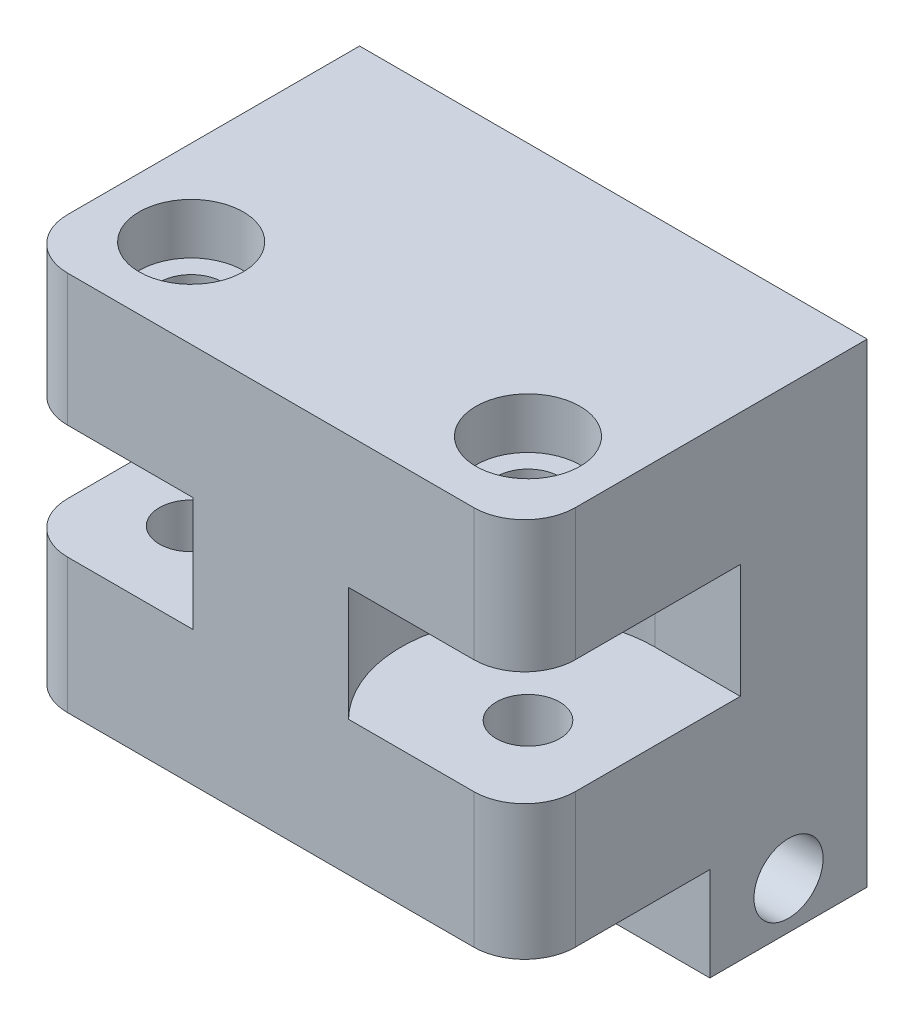
SolidWorks part; units mm, degrees
ref_plane "Front Plane" through (0, 0, 0) normal (0, 0, 1) x (1, 0, 0)
ref_plane "Top Plane" through (0, 0, 0) normal (0, 1, 0) x (1, 0, 0)
ref_plane "Right Plane" through (0, 0, 0) normal (1, 0, 0) x (0, 0, -1)
sketch "Sketch1" plane through (0, 0, 0) normal (0, 1, 0) x (1, 0, 0)
  line L1 (-22.8462, -9.1868) -> (17.1538, -9.1868)
  line L2 (-22.8462, -9.1868) -> (-22.8462, 17.8132)
  line L3 (-22.8462, 17.8132) -> (17.1538, 17.8132)
  line L4 (17.1538, -9.1868) -> (17.1538, 17.8132)
  dimension "D1" = 27
  dimension "D2" = 40
extrude "Boss-Extrude1" add sketch "Sketch1" along normal blind 30
sketch "Sketch2" plane through (0, 0, -17.8132) normal (0, 0, -1) x (-1, 0, 0)
  line L0 (2.8462, 30) -> (2.8462, 0) construction
  line L1 (-8.0864, 4) -> (-0.2064, 4)
  line L2 (-0.2064, 4) -> (-0.2064, 7)
  line L3 (-0.2064, 7) -> (-2.8664, 7)
  line L4 (-2.8664, 7) -> (-2.8664, 8.0087)
  line L5 (-2.8664, 8.0087) -> (-0.2538, 10.6287)
  line L6 (-0.2538, 10.6287) -> (5.9462, 10.6287)
  line L7 (-17.1538, 30) -> (22.8462, 30) construction
  line L8 (-17.1538, 0) -> (22.8462, 0) construction
  line L9 (-8.0864, 4) -> (-8.0864, 26)
  line L10 (-8.0864, 26) -> (-0.2064, 26)
  line L11 (-0.2064, 26) -> (-0.2064, 23)
  line L12 (-0.2064, 23) -> (-2.8664, 23)
  line L13 (-2.8664, 23) -> (-2.8664, 21.9913)
  line L14 (-2.8664, 21.9913) -> (-0.2464, 19.3787)
  line L15 (-0.2464, 19.3787) -> (5.9536, 19.3787)
  line L16 (-17.1538, 15) -> (22.8462, 15) construction
  line L17 (-17.1538, 30) -> (-17.1538, 0) construction
  line L18 (22.8462, 30) -> (22.8462, 0) construction
  line L19 (5.9387, 19.3787) -> (-0.2613, 19.3787)
  line L20 (8.5587, 21.9913) -> (5.9387, 19.3787)
  line L21 (8.5587, 23) -> (8.5587, 21.9913)
  line L22 (5.8987, 23) -> (8.5587, 23)
  line L23 (5.8987, 26) -> (5.8987, 23)
  line L24 (13.7787, 26) -> (5.8987, 26)
  line L25 (13.7787, 4) -> (13.7787, 26)
  line L26 (8.5587, 8.0087) -> (5.9462, 10.6287)
  line L27 (8.5587, 7) -> (8.5587, 8.0087)
  line L28 (5.8987, 7) -> (8.5587, 7)
  line L29 (5.8987, 4) -> (5.8987, 7)
  line L30 (13.7787, 4) -> (5.8987, 4)
  point P26 (-8.0864, 15)
  point P27 (2.8462, 15)
  point P37 (2.8462, 10.6287)
  dimension "D1" = 6.2
  dimension "D2" = 2.62
  dimension "D3" = 3.7
  dimension "D4" = 8.75
  dimension "D5" = 7.88
  dimension "D6" = 22
  dimension "D7" = 5.22
  dimension "D8" = 3
  dimension "D9" = 90
extrude "Cut-Extrude1" cut sketch "Sketch2" against normal blind 10 contours L30 L25 L24 L23 L22 L21 L20 L15 L14 L13 L12 L11 L10 L9 L1 L2 L3 L4 L5 L6 L26 L27 L28 L29 region at (-2.8462, 15.0011, -17.8132)
sketch "Sketch3" plane through (0, 0, 0) normal (0, -1, 0) x (1, 0, 0)
  line L0 (-22.8462, 9.1868) -> (17.1538, 9.1868) construction
  line L1 (17.1538, 9.1868) -> (17.1538, -17.8132) construction
  line L2 (-2.8462, 9.1868) -> (-2.8462, -17.8132) construction
  line L3 (17.1538, -17.8132) -> (-22.8462, -17.8132) construction
  circle A0 centre (10.4238, 2.1868) radius 2.5
  circle A2 centre (-16.1162, 2.1868) radius 2.5
  dimension "D1" = 5
  dimension "D3" = 7
  dimension "D4" = 6.73
extrude "Cut-Extrude2" cut sketch "Sketch3" against normal blind 30
sketch "Sketch8" plane through (0, 0, 0) normal (0, -1, 0) x (1, 0, 0)
  line L0 (3.2824, 9.1868) -> (17.1538, 9.1868)
  line L1 (-22.8462, 9.1868) -> (17.1538, 9.1868) construction
  line L2 (17.1538, 9.1868) -> (17.1538, -7.8132)
  line L3 (17.1538, 9.1868) -> (17.1538, -17.8132) construction
  line L4 (17.1538, -7.8132) -> (10.4238, -7.8132)
  line L6 (-2.8462, -17.8132) -> (-2.8462, 9.1868) construction
  line L7 (17.1538, -17.8132) -> (-22.8462, -17.8132) construction
  line L8 (-22.8462, -7.8132) -> (-16.1162, -7.8132)
  line L9 (-22.8462, 9.1868) -> (-22.8462, -7.8132)
  line L10 (-8.9747, 9.1868) -> (-22.8462, 9.1868)
  arc A0 (10.4238, -7.8132) -> (3.2824, 9.1868) centre (10.4238, 2.1868) cw
  arc A1 (-16.1162, -7.8132) -> (-8.9747, 9.1868) centre (-16.1162, 2.1868) ccw
  point P20 (10.4238, -7.3132)
  circle M6 centre (10.4238, 2.1868) radius 2.5
  circle M7 centre (-16.1162, 2.1868) radius 2.5
  line M8 (-22.8462, 9.1868) -> (-22.8462, -17.8132)
  line M10 (17.1538, -17.8132) -> (17.1538, 9.1868)
  line M11 (17.1538, 9.1868) -> (-22.8462, 9.1868)
  dimension "D1" = 10
extrude "Cut-Extrude5" cut sketch "Sketch8" against normal blind 9 from offset 10.62 contours A0 L4 M10 M11 M6 | M6 | L8 A1 M11 M8 M7 | M7 region at (10.2181, 0, 8.9483) region at (-7.1165, 0, -1.5938) region at (10.4238, 0, 2.1868) region at (-16.1162, 0, 2.1868) offset against normal yes
sketch "Sketch10" plane through (8.0864, 0, 0) normal (-1, 0, 0) x (0, 0, 1)
  line L0 (-17.8132, 30) -> (-17.8132, 0) construction
  line L1 (-17.8132, 19.62) -> (2.1868, 19.62)
  line L2 (-17.8132, 19.62) -> (-17.8132, 10.62)
  line L3 (-17.8132, 10.62) -> (2.1868, 10.62)
  line L4 (2.1868, 19.62) -> (2.1868, 10.62)
  line L6 (9.1868, 19.62) -> (-7.8132, 19.62) construction
  line L7 (9.1868, 10.62) -> (-7.8132, 10.62) construction
  point P6 (2.1868, 19.62)
  point P9 (2.1868, 10.62)
  dimension "D1" = 20
extrude "Cut-Extrude7" cut sketch "Sketch10" along normal blind 6.8
sketch "Sketch12" plane through (-13.7787, 0, 0) normal (1, 0, 0) x (0, 0, -1)
  line L0 (-9.1868, 19.62) -> (1.8761, 19.62) construction
  line L1 (17.8132, 19.62) -> (-2.1868, 19.62)
  line L2 (17.8132, 19.62) -> (17.8132, 10.62)
  line L3 (17.8132, 10.62) -> (-2.1868, 10.62)
  line L4 (-2.1868, 19.62) -> (-2.1868, 10.62)
  line L6 (7.8132, 10.62) -> (-9.1868, 10.62) construction
  line L7 (17.8132, 30) -> (17.8132, 0) construction
  point P4 (-2.2326, 19.62)
  point P7 (-2.4075, 10.62)
  point P10 (0, 0)
  point P11 (17.8132, 19.62)
  dimension "D1" = 20
extrude "Cut-Extrude10" cut sketch "Sketch12" along normal blind 6.8
fillet "Fillet1" radius 4 4 edges at (17.1538, 5.31, 9.1868) (17.1538, 24.81, 9.1868) (-22.8462, 5.31, 9.1868) (-22.8462, 24.81, 9.1868)
sketch "Sketch13" plane through (17.1538, 0, 0) normal (1, 0, 0) x (0, 0, -1)
  line L0 (-5.1868, 0) -> (17.8132, 0) construction
  line L1 (17.8132, 30) -> (17.8132, 0) construction
  line L3 (17.8132, 0) -> (5.4132, 0)
  line L4 (17.8132, 0) -> (17.8132, -7.4)
  line L5 (17.8132, -7.4) -> (5.4132, -7.4)
  line L6 (5.4132, 0) -> (5.4132, -7.4)
  circle A0 centre (11.6132, -3.7) radius 2.725
  dimension "D1" = 6.2
  dimension "D2" = 3.7
  dimension "D3" = 5.45
  dimension "D4" = 12.4
  dimension "D5" = 7.4
extrude "Boss-Extrude2" add sketch "Sketch13" against normal up to surface (40 mm away) up to face at (-22.8462, 15.06, -3.8132)
sketch "Sketch14" plane through (0, 0, -5.4132) normal (0, 0, 1) x (1, 0, 0)
  line L0 (-22.8462, -7.4) -> (17.1538, -7.4) construction
  line L1 (-12.8462, -7.4) -> (7.1538, -7.4)
  line L2 (-12.8462, -7.4) -> (-12.8462, 0)
  line L3 (-12.8462, 0) -> (7.1538, 0)
  line L4 (7.1538, -7.4) -> (7.1538, 0)
  line L5 (-18.8462, 0) -> (13.1538, 0) construction
  line L7 (17.1538, 0) -> (17.1538, -7.4) construction
  dimension "D1" = 20
  dimension "D2" = 10
extrude "Cut-Extrude11" cut sketch "Sketch14" against normal up to next
sketch "Sketch15" plane through (0, 30, 0) normal (0, 1, 0) x (1, 0, 0)
  line L0 (-2.8462, 17.8132) -> (-2.8462, -9.1868) construction
  line L13 (17.1538, 17.8132) -> (-22.8462, 17.8132) construction
  line L14 (-18.8462, -9.1868) -> (13.1538, -9.1868) construction
  circle A4 centre (-16.1162, -2.1868) radius 4.1
  circle A5 centre (10.4238, -2.1868) radius 4.1
  dimension "D1" = 8.2
extrude "Cut-Extrude12" cut sketch "Sketch15" against normal blind 4
sketch "Sketch16" plane through (0, 0, 0) normal (0, -1, 0) x (1, 0, 0)
  line L1 (-13.749, -1.9132) -> (-11.3819, 2.1868)
  line L2 (-11.3819, 2.1868) -> (-13.749, 6.2868)
  line L3 (-13.749, 6.2868) -> (-18.4833, 6.2868)
  line L4 (-18.4833, 6.2868) -> (-20.8504, 2.1868)
  line L5 (-20.8504, 2.1868) -> (-18.4833, -1.9132)
  line L6 (-18.4833, -1.9132) -> (-13.749, -1.9132)
  line L7 (12.791, -1.9132) -> (15.1581, 2.1868)
  line L8 (15.1581, 2.1868) -> (12.791, 6.2868)
  line L9 (12.791, 6.2868) -> (8.0567, 6.2868)
  line L10 (8.0567, 6.2868) -> (5.6896, 2.1868)
  line L11 (5.6896, 2.1868) -> (8.0567, -1.9132)
  line L12 (8.0567, -1.9132) -> (12.791, -1.9132)
  circle A0 centre (10.4238, 2.1868) radius 2.5 construction
  circle A1 centre (-16.1162, 2.1868) radius 2.5 construction
  circle A2 centre (10.4238, 2.1868) radius 2.5
  circle A3 centre (-16.1162, 2.1868) radius 2.5
  circle A4 centre (-16.1162, 2.1868) radius 4.1 construction
  circle A5 centre (10.4238, 2.1868) radius 4.1 construction
  dimension "D1" = 8.2
  dimension "D2" = 8.2
extrude "Cut-Extrude13" cut sketch "Sketch16" against normal blind 4
